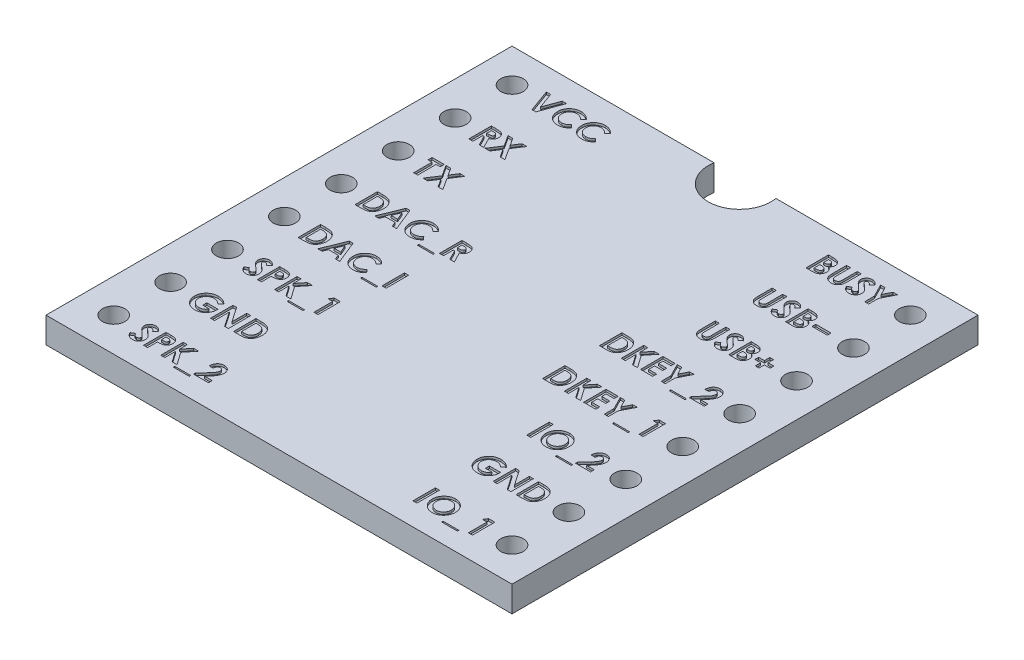
SolidWorks part; units mm, degrees
ref_plane "Front Plane" through (0, 0, 0) normal (0, 0, 1) x (1, 0, 0)
ref_plane "Top Plane" through (0, 0, 0) normal (0, 1, 0) x (1, 0, 0)
ref_plane "Right Plane" through (0, 0, 0) normal (1, 0, 0) x (0, 0, -1)
sketch "Sketch1" plane through (0, 0, 0) normal (0, 1, 0) x (1, 0, 0)
  line L1 (-8.89, -8.89) -> (8.89, -8.89) construction
  line L2 (-8.89, -8.89) -> (-8.89, 8.89) construction
  line L3 (-8.89, 8.89) -> (8.89, 8.89) construction
  line L4 (8.89, -8.89) -> (8.89, 8.89) construction
  line L5 (-8.89, -8.89) -> (8.89, 8.89) construction
  line L6 (-8.89, 8.89) -> (8.89, -8.89) construction
  line L7 (-10.4, 10.4) -> (10.4, 10.4)
  line L8 (-10.4, 10.4) -> (-10.4, -10.4)
  line L9 (-10.4, -10.4) -> (10.4, -10.4)
  line L10 (10.4, 10.4) -> (10.4, -10.4)
  line L11 (-10.4, 10.4) -> (10.4, -10.4) construction
  line L12 (-10.4, -10.4) -> (10.4, 10.4) construction
  circle A0 centre (-8.89, -8.89) radius 0.4
  circle A1 centre (8.89, -8.89) radius 0.4
  point P0 (0, 0)
  point P5 (0, 0)
  dimension "D3" = 0.8
  dimension "D4" = 0.8
  dimension "D1" = 17.78
  dimension "D2" = 20.8
extrude "Boss-Extrude1" add sketch "Sketch1" along normal blind 1.15
hole_wizard "Ø1.0 (1) Diameter Hole2" positions "Sketch4" profile "Sketch5" hole size "Ø1.0" standard "ANSI Metric" end condition through all
sketch "Sketch4" plane through (0, 1.15, 0) normal (0, 1, 0) x (1, 0, 0)
  point P0 (-8.89, -8.89)
  point P3 (8.89, -8.89)
  point P10 (-8.89, -6.35)
  point P11 (8.89, -6.35)
  point P12 (-8.89, -3.81)
  point P13 (8.89, -3.81)
  point P14 (-8.89, -1.27)
  point P15 (8.89, -1.27)
  point P16 (-8.89, 1.27)
  point P17 (8.89, 1.27)
  point P18 (-8.89, 3.81)
  point P19 (8.89, 3.81)
  point P20 (-8.89, 6.35)
  point P21 (8.89, 6.35)
  point P22 (-8.89, 8.89)
  point P23 (8.89, 8.89)
  dimension "D1" = 8
sketch "Sketch5" plane through (-8.89, 1.15, 8.89) normal (1, 0, 0) x (0, 0, 1)
  line L0 (0, 0) -> (0, 1.15)
  line L1 (0, 1.15) -> (0.5, 1.15)
  line L2 (0.5, 1.15) -> (0.5, 0)
  line L5 (0.5, 0) -> (0, 0)
  line L11 (0, -6.35) -> (0, 107.95) construction
  dimension "Thru Hole Dia." = 1
  dimension "Thru Hole Depth" = 1.15
sketch "Sketch6" plane through (0, 1.15, 0) normal (0, 1, 0) x (1, 0, 0)
  line L0 (0, 10.4) -> (0, 10.16) construction
  line L1 (10.4, 10.4) -> (-10.4, 10.4) construction
  circle A0 centre (0, 10.16) radius 1.4
  dimension "D1" = 0.24
  dimension "D2" = 2.8
extrude "Cut-Extrude1" cut sketch "Sketch6" against normal blind 10
sketch "Sketch7" plane through (0, 1.15, 0) normal (0, 1, 0) x (1, 0, 0)
  line L1 (-7.89, 8.39) -> (-3.3136, 8.39) construction
  line L2 (2.1529, 8.39) -> (7.89, 8.39) construction
  circle A0 centre (-8.89, 8.89) radius 0.5 construction
  circle A1 centre (8.89, 8.89) radius 0.5 construction
  text T0 "VCC\r\nRX\r\nTX\r\nDAC_R\r\nDAC_I\r\nSPK_1\r\nGND\r\nSPK_2" font "Century Gothic" height 1
  text T1 "BUSY\r\nUSB−\r\nUSB+\r\nADKEY_2\r\nADKEY_1\r\nIO_2\r\nGND\r\nIO_1" font "Century Gothic" height 1
  point P10 (2.1529, 8.39)
  dimension "D1" = 1
  dimension "D2" = 0.5
  dimension "D3" = 1
extrude "Cut-Extrude2" cut sketch "Sketch7" against normal blind 0.1
